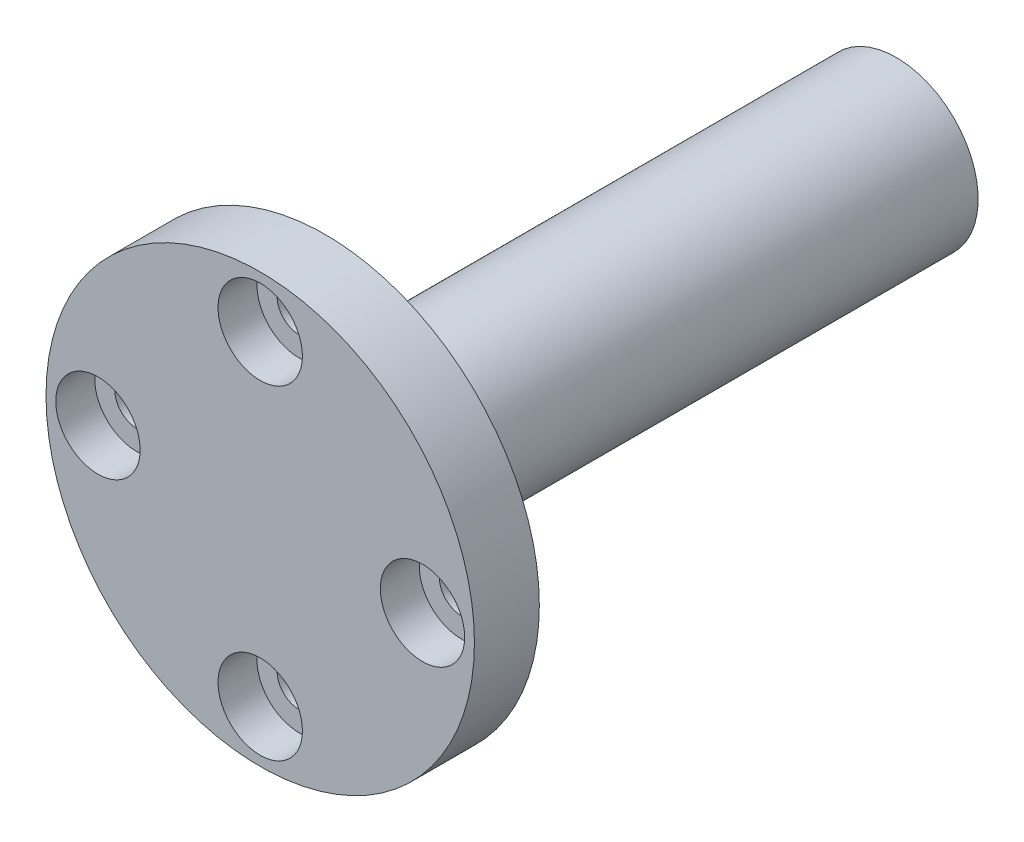
SolidWorks part; units mm, degrees
material "3.1355 (EN-AW 2024)"
ref_plane "Front" through (0, 0, 0) normal (0, 0, 1) x (1, 0, 0)
ref_plane "Top" through (0, 0, 0) normal (0, 1, 0) x (1, 0, 0)
ref_plane "Right" through (0, 0, 0) normal (1, 0, 0) x (0, 0, -1)
sketch "Эскиз2" plane through (0, 0, 0) normal (1, 0, 0) x (0, 0, -1)
  line L0 (0, 0) -> (0, 16.5)
  line L1 (0, 16.5) -> (5, 16.5)
  line L2 (5, 16.5) -> (5, 6.3)
  line L3 (5, 6.3) -> (49, 6.3)
  line L4 (49, 6.3) -> (49, 0)
  line L5 (49, 0) -> (0, 0)
  dimension "D1" = 16.5
  dimension "D2" = 5
  dimension "D3" = 6.3
  dimension "D4" = 44
  dimension "D5" = 49
revolve "Повернуть1" add sketch "Эскиз2" angle 360 about L5
sketch "Эскиз3" plane through (0, 0, 0) normal (0, 0, 1) x (1, 0, 0)
  circle A0 centre (0, 0) radius 12.5 construction
  point P3 (0, 12.5)
  point P7 (12.5, 0)
  point P8 (0, -12.5)
  point P9 (-12.5, 0)
  point P10 (0, 0)
  dimension "D1" = 25
  dimension "D2" = 4
hole_wizard "Цековка для винта с внутренним шестигранником M31" positions "Эскиз5" profile "Эскиз4" counterbore size "M3" standard "Ansi Metric" end condition through all
sketch "Эскиз5" plane through (0, 0, 0) normal (0, 0, 1) x (1, 0, 0)
  point P0 (-12.5, 0)
  point P3 (0, 12.5)
  point P6 (12.5, 0)
  point P9 (0, -12.5)
sketch "Эскиз4" plane through (-12.5, 0, 0) normal (1, 0, 0) x (0, -1, 0)
  line L0 (0, 0) -> (0, 49)
  line L1 (0, 49) -> (1.7, 49)
  line L3 (1.7, 49) -> (1.7, 3)
  line L4 (1.7, 3) -> (3.25, 3)
  line L5 (3.25, 3) -> (3.25, 0)
  line L7 (3.25, 0) -> (0, 0)
  line L11 (0, -6.35) -> (0, 107.95) construction
  dimension "Диаметр сквозного отверстия" = 3.4
  dimension "Глубина сквозного отверстия" = 49
  dimension "Диаметр цековки" = 6.5
  dimension "Глубина цековки" = 3
hole_wizard "Отверстие обработанное метчиком M3x0.51" positions "Эскиз6" profile "Эскиз7" tap size "M3x0.5" standard "Ansi Metric"
sketch "Эскиз6" plane through (2.7067, -7.2328, -49) normal (0, 0, -1) x (-0.6355, -0.7721, 0)
  point P0 (-3.8641, 6.6864)
sketch "Эскиз7" plane through (0, 0, -49) normal (1, 0, 0) x (0, 1, 0)
  line L0 (0, 0) -> (0, 15.7511)
  line L1 (0, 15.7511) -> (1.25, 15)
  line L2 (1.25, 15) -> (1.25, 0)
  line L3 (1.25, 0) -> (0, 0)
  line L4 (0, 15.7511) -> (-1.25, 15) construction
  line L5 (0, -6.35) -> (0, 107.95) construction
  dimension "Диаметр сверла" = 2.5
  dimension "Глубина сверла" = 15
  dimension "Угол заточки сверла" = 118
cosmetic thread "Отверстие резьбы1" parameters "D1"=13, "D2"=3
